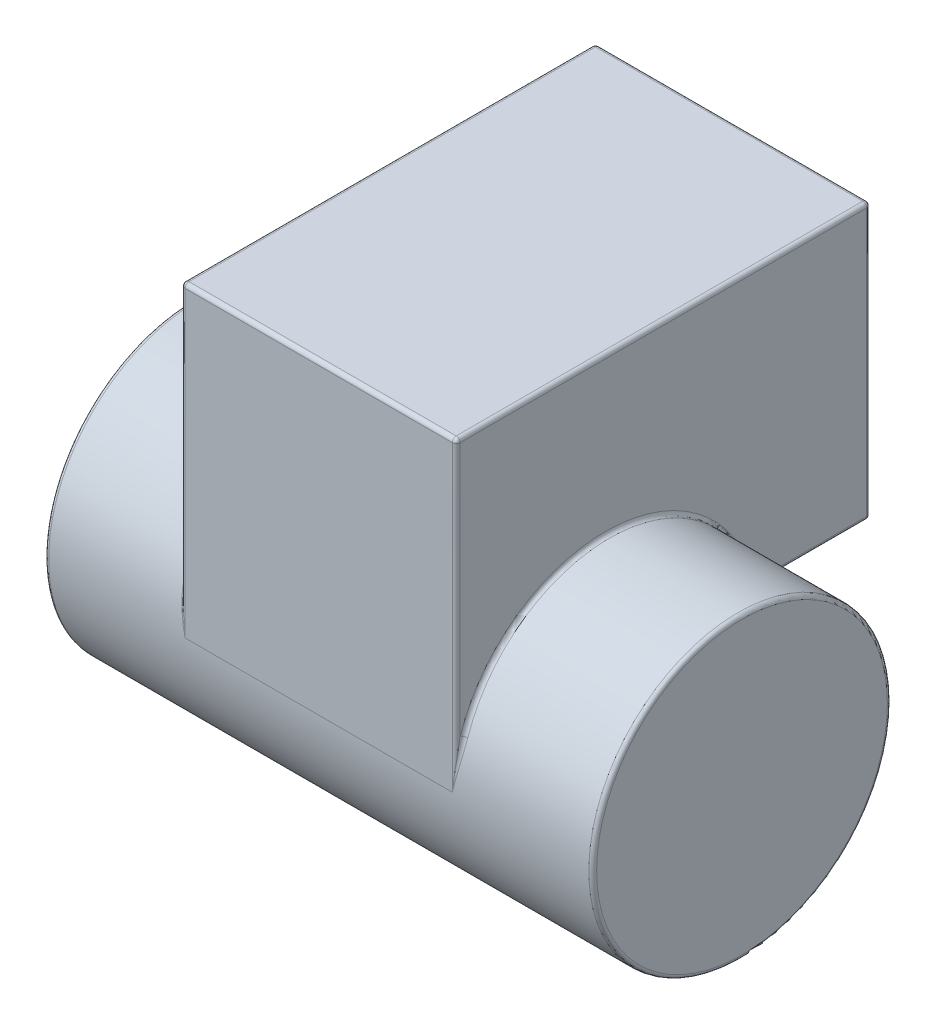
SolidWorks part; units mm, degrees
ref_plane "Plan de face" through (0, 0, 0) normal (0, 0, 1) x (1, 0, 0)
ref_plane "Plan de dessus" through (0, 0, 0) normal (0, 1, 0) x (1, 0, 0)
ref_plane "Plan de droite" through (0, 0, 0) normal (1, 0, 0) x (0, 0, -1)
sketch "Sketch1" plane through (0, 0, 0) normal (1, 0, 0) x (0, 0, -1)
  circle A0 centre (0, 0) radius 38
  dimension "D1" = 76
extrude "Boss-Extrude1" add sketch "Sketch1" along normal mid plane 139.5
sketch "Sketch2" plane through (0, 0, 0) normal (1, 0, 0) x (0, 0, -1)
  line L0 (-38, 0) -> (-38, 78.0544)
  line L5 (-38, 78.0544) -> (67.454, 78.0544)
  line L6 (67.454, 78.0544) -> (67.454, 8.0544)
  line L7 (67.454, 8.0544) -> (43.8249, 8.0544)
  line L8 (43.8249, 8.0544) -> (37.9577, 1.7923)
  circle A1 centre (0, 0) radius 38
  arc A2 (-38, 0) -> (37.9577, 1.7923) centre (0, 0) ccw
  dimension "D2" = 70
  dimension "D1" = 0
extrude "Boss-Extrude2" add sketch "Sketch2" along normal mid plane 70
fillet "Fillet1" radius 1 19 edges at (-69.75, 0, -38) (69.75, 0, -38) (35, 37.9894, 0.8964) (-35, 37.9894, 0.8964) (0, 1.7923, -37.9577) (0, 8.0544, -43.8249) (0, 8.0544, -67.454) (0, 78.0544, -67.454) (0, 78.0544, 38) (35, 39.0272, 38) (35, 78.0544, -14.727) (35, 43.0544, -67.454) (35, 8.0544, -55.6395) (35, 4.9233, -40.8913) (-35, 39.0272, 38) (-35, 78.0544, -14.727) (-35, 43.0544, -67.454) (-35, 8.0544, -55.6395) (-35, 4.9233, -40.8913)
sketch "Sketch6" plane through (0, 0, -67.454) normal (0, 0, -1) x (-1, 0, 0)
  line L0 (-34, 77.0544) -> (34, 9.0544) construction
sketch "Sketch7" plane through (0, 0, 0) normal (1, 0, 0) x (0, 0, -1)
  line L0 (67.454, 43.0544) -> (133.8756, 43.0544) construction
  line L1 (67.454, 77.0544) -> (67.454, 9.0544) construction
